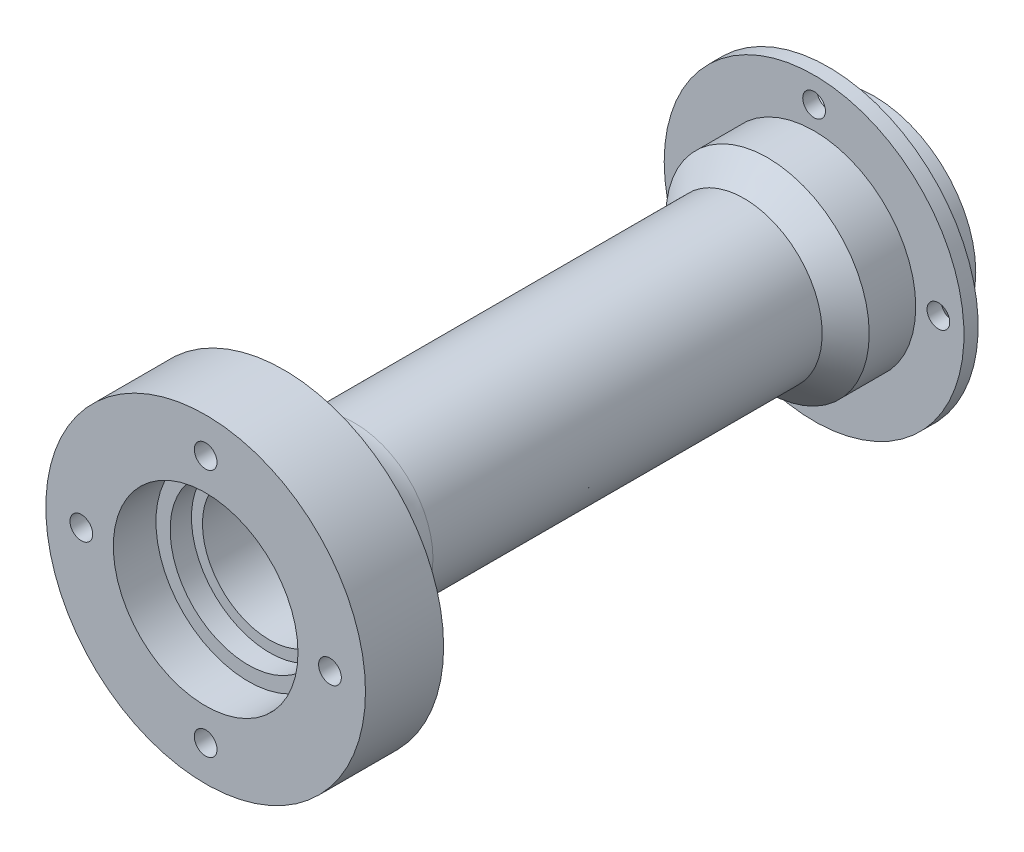
SolidWorks part; units mm, degrees
ref_plane "Front Plane" through (0, 0, 0) normal (0, 0, 1) x (1, 0, 0)
ref_plane "Top Plane" through (0, 0, 0) normal (0, 1, 0) x (1, 0, 0)
ref_plane "Right Plane" through (0, 0, 0) normal (1, 0, 0) x (0, 0, -1)
sketch "Sketch2" plane through (0, 0, 0) normal (0, 0, 1) x (1, 0, 0)
  circle A0 centre (0, 0) radius 11
  circle A1 centre (0, 0) radius 9.45
  dimension "D1" = 22
  dimension "D2" = 1.55
extrude "Boss-Extrude2" add sketch "Sketch2" along normal blind 88.1
sketch "Sketch3" plane through (0, 0, 88.1) normal (0, 0, 1) x (1, 0, 0)
  circle A0 centre (0, 0) radius 22.5
  circle A1 centre (0, 0) radius 11
  dimension "D1" = 45
extrude "Boss-Extrude3" add sketch "Sketch3" against normal blind 5
fillet "Fillet1" radius 10 1 edges at (11, 0, 83.1)
sketch "Sketch4" plane through (0, 0, 88.1) normal (0, 0, 1) x (1, 0, 0)
  circle A0 centre (0, 0) radius 9.45
  circle A1 centre (0, 0) radius 11
  dimension "D1" = 22
extrude "Cut-Extrude1" cut sketch "Sketch4" against normal blind 3
sketch "Sketch7" plane through (0, 0, 0) normal (0, 0, -1) x (-1, 0, 0)
  circle A0 centre (0, 0) radius 14.31
  circle A1 centre (0, 0) radius 11
  dimension "D1" = 28.62
extrude "Boss-Extrude6" add sketch "Sketch7" against normal blind 20
sketch "Sketch8" plane through (0, 0, 0) normal (0, 0, -1) x (-1, 0, 0)
  circle A0 centre (0, 0) radius 11
  dimension "D1" = 22
extrude "Cut-Extrude3" cut sketch "Sketch8" against normal blind 7
ref_plane "Plane2" through (0, 0, 6.45) normal (0, 0, -1) x (-1, 0, 0)
sketch "Sketch10" plane through (0, 0, 6.45) normal (0, 0, -1) x (-1, 0, 0)
  circle A0 centre (0, 0) radius 21.1
  circle A1 centre (0, 0) radius 14.31
  dimension "D1" = 42.2
extrude "Boss-Extrude8" add sketch "Sketch10" against normal blind 2
sketch "Sketch11" plane through (0, 0, 6.45) normal (0, 0, -1) x (-1, 0, 0)
  circle A0 centre (0, 0) radius 17.5
  circle A1 centre (0, 17.5) radius 1.6
  circle A2 centre (17, 0) radius 1.6
  circle A3 centre (-0.5, -17) radius 1.6
  circle A4 centre (-17.5, 0.5) radius 1.6
  point P14 (-0.25, 0.25)
  dimension "D1" = 35
  dimension "D2" = 3.2
  dimension "D3" = 4
extrude "Cut-Extrude4" cut sketch "Sketch11" against normal up to surface (2 mm away) and the other way through all contours A4 | A1 | A3 | A2 up to face at (-14.31, 0, 8.45)
chamfer "Chamfer5" distance 5 angle 45 1 edges at (-14.31, 0, 20)
sketch "Sketch12" plane through (0, 0, 88.1) normal (0, 0, 1) x (1, 0, 0)
  line L1 (-14.1421, -17.5) -> (14.1421, -17.5)
  line L2 (-14.1421, -17.5) -> (-14.1421, 17.5)
  line L3 (-14.1421, 17.5) -> (14.1421, 17.5)
  line L4 (14.1421, -17.5) -> (14.1421, 17.5)
  line L5 (-14.1421, -17.5) -> (14.1421, 17.5) construction
  line L6 (-14.1421, 17.5) -> (14.1421, -17.5) construction
  circle A0 centre (0, 0) radius 22.5 construction
  circle A1 centre (0, 17.5) radius 1.6
  circle A2 centre (17.5, 0) radius 1.6
  circle A3 centre (0, -17.5) radius 1.6
  circle A4 centre (-17.5, 0) radius 1.6
  point P0 (0, 0)
  point P19 (0, 0)
  dimension "D3" = 3.2
  dimension "D1" = 35
  dimension "D2" = 28.2843
  dimension "D4" = 4
extrude "Cut-Extrude5" cut sketch "Sketch12" against normal blind 10 contours A1 | A4 | A3 | A2
sketch "Sketch13" plane through (0, 0, 88.1) normal (0, 0, 1) x (1, 0, 0)
  circle A0 centre (0, 0) radius 11.05
  circle A1 centre (0, 0) radius 13
  circle A2 centre (0, 0) radius 22.5
  circle A3 centre (0, 17.5) radius 1.4087
  circle A4 centre (17.5, 0) radius 1.4087
  circle A5 centre (0, -17.5) radius 1.4087
  circle A6 centre (-17.5, 0) radius 1.4087
  point P16 (0, 0)
  circle M5 centre (0, 17.5) radius 1.6
  circle M6 centre (-17.5, 0) radius 1.6
  circle M7 centre (0, -17.5) radius 1.6
  circle M8 centre (17.5, 0) radius 1.6
  circle M10 centre (0, 0) radius 22.5
  dimension "D1" = 22.1
  dimension "D2" = 26
  dimension "D3" = 4
extrude "Boss-Extrude9" add sketch "Sketch13" along normal blind 6 contours A1 M10 M6 M8 M7 M5 region at (-21.8636, 0, 88.1)
